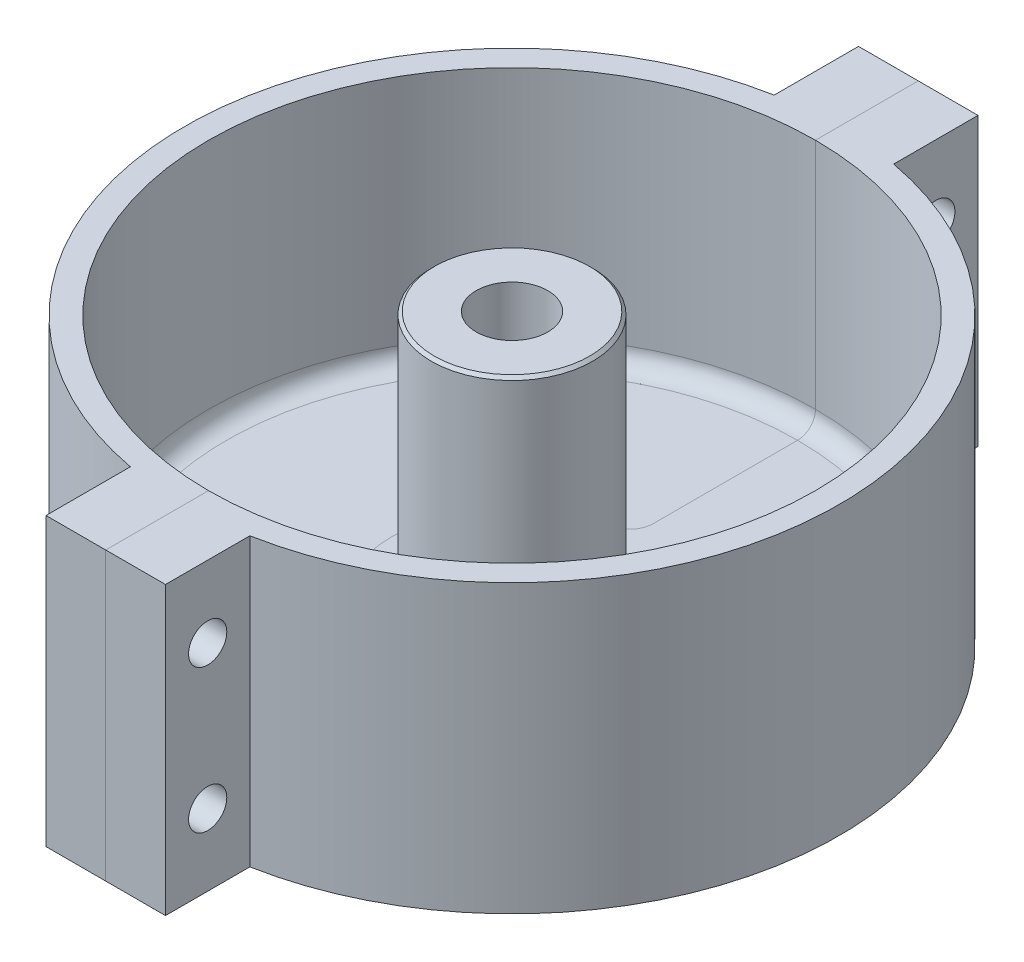
SolidWorks part; units mm, degrees
ref_plane "Front Plane" through (0, 0, 0) normal (0, 0, 1) x (1, 0, 0)
ref_plane "Top Plane" through (0, 0, 0) normal (0, 1, 0) x (1, 0, 0)
ref_plane "Right Plane" through (0, 0, 0) normal (1, 0, 0) x (0, 0, -1)
sketch "Sketch1" plane through (0, 0, 0) normal (0, 1, 0) x (1, 0, 0)
  circle A0 centre (0, 0) radius 25.4
  circle A1 centre (0, 0) radius 27.4
  dimension "D1" = 50.8
  dimension "D2" = 54.8
extrude "Boss-Extrude1" add sketch "Sketch1" along normal blind 24
extrude "Boss-Extrude2" add sketch "Sketch1<2>" along normal blind 3 contours A0 region at (0, 0, 0)
sketch "Sketch1<2>" plane through (0, 0, 0) normal (0, 1, 0) x (1, 0, 0) same geometry as "Sketch1"
fillet "Fillet1" radius 1.5 1 edges at (0, 3, 25.4)
sketch "Sketch2" plane through (0, 3, 0) normal (0, 1, 0) x (1, 0, 0)
  circle A0 centre (0, 0) radius 6.75
  dimension "D1" = 13.5
extrude "Boss-Extrude3" add sketch "Sketch2" along normal blind 21.3
sketch "Sketch3" plane through (0, 24, 0) normal (0, 1, 0) x (1, 0, 0)
  line L0 (0, 0) -> (0, 45.2463) construction
  line L1 (5, 34) -> (-5, 34)
  line L2 (5, 34) -> (5, 26)
  line L3 (5, 26) -> (-5, 26)
  line L4 (-5, 34) -> (-5, 26)
  circle A0 centre (0, 0) radius 27.4 construction
  arc A1 (5, 26.9399) -> (-5, 26.9399) centre (0, 0) ccw
  circle M2 centre (0, 0) radius 27.4
  dimension "D1" = 10
  dimension "D2" = 26
  dimension "D3" = 8
extrude "Boss-Extrude4" add sketch "Sketch3" against normal up to surface (24 mm away) contours A1 L0 L1 L4 | L0 L2 L1 M2 region at (-2.5283, 24, -30.6222) region at (2.5283, 24, -30.6222) up to face at (0, 0, 27.4)
hole_wizard "M3 Clearance Hole1" positions "Sketch5" profile "Sketch7" hole size "M3" standard "ANSI Metric" end condition through all
sketch "Sketch5" plane through (-5, 0, 0) normal (-1, 0, 0) x (0, 0, 1)
  line L0 (-34, 24) -> (-26.9399, 24) construction
  line L1 (-34, 24) -> (-26.9399, 24)
  line L2 (-26.9399, 0) -> (-34, 0) construction
  point P0 (-30.47, 18)
  point P2 (-30.47, 6)
  point P7 (-30.47, 24)
  dimension "D1" = 6
  dimension "D2" = 6
sketch "Sketch7" plane through (-5, 18, -30.47) normal (0, 1, 0) x (0, 0, 1)
  line L0 (0, 0) -> (0, 32.4)
  line L1 (0, 32.4) -> (1.6, 32.4)
  line L2 (1.6, 32.4) -> (1.6, 0)
  line L5 (1.6, 0) -> (0, 0)
  line L11 (0, -6.35) -> (0, 107.95) construction
  dimension "Thru Hole Dia." = 3.2
  dimension "Thru Hole Depth" = 32.4
chamfer "Chamfer1" distance 1 angle 45 1 edges at (0, 3, 6.75)
mirror "Mirror1" about plane through (0, 0, 0) normal (0, 0, 1) of "Boss-Extrude4", "M3 Clearance Hole1"
sketch "Sketch8" plane through (0, 24, 0) normal (0, 1, 0) x (1, 0, 0)
  line L0 (0, 34) -> (0, 11.8322)
  line L1 (5, 34) -> (-5, 34) construction
  line L2 (0, -34) -> (0, -11.8322)
  line L3 (5, -34) -> (-5, -34) construction
  arc A0 (-1.6667, 9.8601) -> (-1.6667, -9.8601) centre (0, 0) ccw
  arc A1 (0, -11.8322) -> (-1.6667, -9.8601) centre (-2, -11.8322) ccw
  arc A2 (0, 11.8322) -> (-1.6667, 9.8601) centre (-2, 11.8322) cw
  point P15 (0, 10)
  dimension "D1" = 20
  dimension "D2" = 2
sketch "Sketch9" plane through (0, 24, 0) normal (0, 1, 0) x (1, 0, 0)
  line L0 (25.3851, 0.8702) -> (24.15, 1)
  line L1 (24.15, 1) -> (24.15, -1)
  line L2 (24.15, -1) -> (25.3851, -0.8702)
  line L3 (0, 0) -> (33.465, 0) construction
  circle A1 centre (0, 0) radius 25.4 construction
  circle A2 centre (0, 0) radius 25.4
  circle A3 centre (0, 0) radius 25.4 construction
  point P6 (25.4, 0)
  circle M9 centre (0, 0) radius 25.4
  dimension "D1" = 1.25
  dimension "D2" = 2
  dimension "D3" = 84
extrude "Boss-Extrude5" [suppressed] add sketch "Sketch9" against normal up to surface (21 mm away) contours L3 L1 L2 A2 | L1 L3 L0 M9 up to face at (0, 3, 7.75)
fillet "Fillet2" [suppressed] radius 0.5
pattern_circular "CirPattern1" [suppressed] count 28 over 360 of bodies 109
split "Split1" trim tools "Sketch8" bodies to split 106 resulting bodies 107 108
chamfer "Chamfer3" distance 0.25 angle 45 1 edges at (0, 24.3, 6.75)
hole_wizard "1/4-20 Tapped Hole1" positions "Sketch10" profile "Sketch12" tap size "1/4-20" standard "ANSI Inch" end condition through all
sketch "Sketch10" plane through (0, 24.3, 0) normal (0, 1, 0) x (1, 0, 0)
  point P0 (0, 0)
sketch "Sketch12" plane through (0, 24.3, 0) normal (1, 0, 0) x (0, 0, 1)
  line L0 (0, 0) -> (0, 24.3)
  line L1 (0, 24.3) -> (3, 24.3)
  line L2 (3, 24.3) -> (3, 0)
  line L5 (3, 0) -> (0, 0)
  line L11 (0, -6.35) -> (0, 107.95) construction
  dimension "Thru Tap Drill Dia." = 6
  dimension "Thru Tap Drill Depth" = 24.3
cosmetic thread "Hole Thread1" parameters "D2"=6.35
